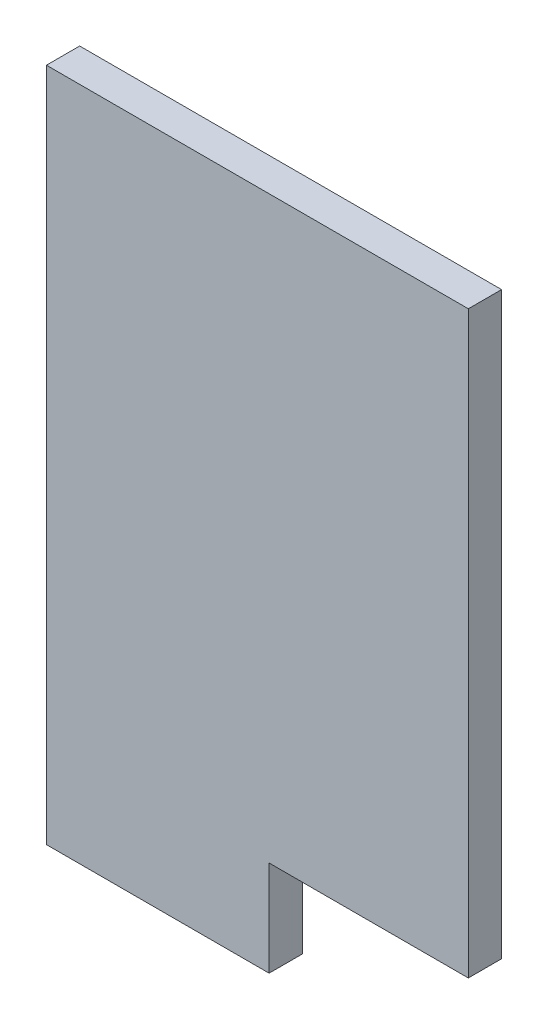
SolidWorks part; units mm, degrees
ref_plane "Front Plane" through (0, 0, 0) normal (0, 0, 1) x (1, 0, 0)
ref_plane "Top Plane" through (0, 0, 0) normal (0, 1, 0) x (1, 0, 0)
ref_plane "Right Plane" through (0, 0, 0) normal (1, 0, 0) x (0, 0, -1)
ref_axis "Axis1" through (0, 0, 0) along (0, 0, 1)
ref_axis "Axis2" through (0, 0, 0) along (0, 1, 0)
ref_axis "Axis3" through (0, 0, 0) along (1, 0, 0)
sketch "Sketch1" plane through (0, 0, 0) normal (0, 0, 1) x (1, 0, 0)
  line L0 (-9.7866, -26.6421) -> (-9.7866, -34.2621) construction
  line L1 (-15.24, 9.7028) -> (6.096, 9.7028)
  line L2 (-15.24, 9.7028) -> (-15.24, -23.3172)
  line L3 (-15.24, -23.3172) -> (6.096, -23.3172)
  line L4 (6.096, 9.7028) -> (6.096, -23.3172)
  line L5 (-15.24, 0) -> (6.096, 0) construction
  line L6 (0, 9.7028) -> (0, -23.3172) construction
  line L7 (-3.5, -19.7358) -> (3.5, -19.7358)
  line L8 (-3.5, -19.7358) -> (-3.5, -23.3172)
  line L10 (3.5, -19.7358) -> (3.5, -23.3172)
  circle A0 centre (-3.9256, 0) radius 0.3556
  circle A2 centre (3.9256, 0) radius 0.3556
  circle A3 centre (-7.2466, -28.5471) radius 1.1874
  circle A4 centre (-8.7706, -26.6421) radius 0.4953
  circle A5 centre (-10.8026, -26.6421) radius 0.4953
  circle A6 centre (-12.3266, -28.5471) radius 1.1874
  circle A7 centre (-7.2466, -34.2621) radius 1.1874
  circle A8 centre (-12.3266, -34.2621) radius 1.1874
  circle A9 centre (-9.7866, -34.2621) radius 0.4953
  dimension "D4" = 0.7112
  dimension "D10" = 2.3749
  dimension "D13" = 0.9906
  dimension "D1" = 21.336
  dimension "D2" = 33.02
  dimension "D3" = 7.8511
  dimension "D5" = 6.096
  dimension "D6" = 9.7028
  dimension "D7" = 19.7358
  dimension "D8" = 7
  dimension "D9" = 28.5471
  dimension "D11" = 5.08
  dimension "D12" = 2.032
  dimension "D14" = 5.715
  dimension "D15" = 1.905
  dimension "D16" = 9.7866
sketch "Sketch2" plane through (0, 0, 0) normal (0, 0, 1) x (1, 0, 0)
  line L0 (-14.732, 9.1948) -> (-14.732, -23.3172)
  line L1 (-14.732, -23.3172) -> (-4.008, -23.3172)
  line L2 (-4.008, -23.3172) -> (-4.008, -18.7198)
  line L3 (-4.008, -18.7198) -> (5.588, -18.7198)
  line L7 (5.588, -18.7198) -> (5.588, 9.1948)
  line L8 (-3.5, -19.7358) -> (3.5, -19.7358) construction
  line L9 (5.588, 9.1948) -> (-14.732, 9.1948)
  line L10 (0, 9.7028) -> (0, -23.3172) construction
  line L11 (0, 9.7028) -> (0, -23.3172) construction
  line L12 (-3.5, -19.7358) -> (-3.5, -23.3172) construction
  line L13 (-14.732, 9.1948) -> (-14.732, 9.7028) construction
  line L14 (-15.24, 9.7028) -> (6.096, 9.7028) construction
  line L15 (-14.732, 9.1948) -> (-15.24, 9.1948) construction
  line L16 (-15.24, 9.7028) -> (-15.24, -23.3172) construction
  line L17 (5.588, 9.1948) -> (6.096, 9.1948) construction
  line L18 (6.096, 9.7028) -> (6.096, -23.3172) construction
  line L19 (-15.24, -23.3172) -> (6.096, -23.3172) construction
  circle A0 centre (-3.9256, 0) radius 0.762 construction
  circle A1 centre (3.9256, 0) radius 0.762 construction
  dimension "D1" = 1.524
  dimension "D2" = 1.016
  dimension "D3" = 0.508
  dimension "D4" = 0.508
extrude "Boss-Extrude1" add sketch "Sketch2" along normal blind 1.6002
